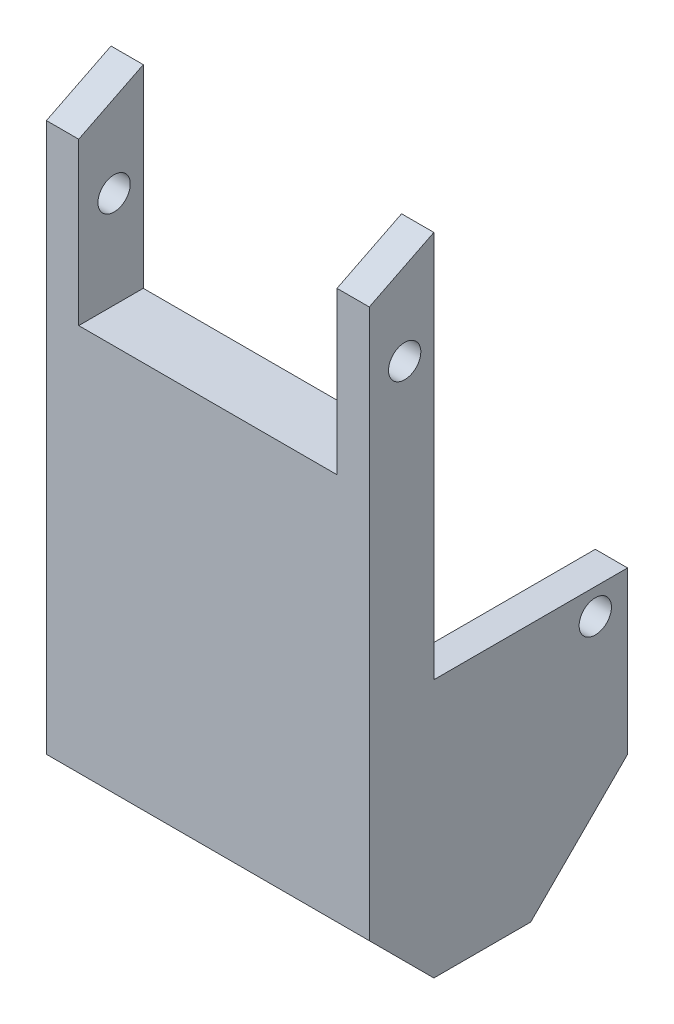
SolidWorks part; units mm, degrees
ref_plane "前视基准面" through (0, 0, 0) normal (0, 0, 1) x (1, 0, 0)
ref_plane "上视基准面" through (0, 0, 0) normal (0, 1, 0) x (1, 0, 0)
ref_plane "右视基准面" through (0, 0, 0) normal (1, 0, 0) x (0, 0, -1)
other "Configuration Table"
sketch "草图1" plane through (0, 0, 0) normal (0, 0, 1) x (1, 0, 0)
  line L1 (2.5, 5) -> (-2.5, 5)
  line L2 (2.5, 5) -> (2.5, -5)
  line L3 (2.5, -5) -> (-2.5, -5)
  line L4 (-2.5, 5) -> (-2.5, -5)
  line L5 (2.5, 5) -> (-2.5, -5) construction
  line L6 (2.5, -5) -> (-2.5, 5) construction
  point P0 (0, 0)
  dimension "D1" = 5
  dimension "D2" = 10
extrude "凸台-拉伸1" add sketch "草图1" along normal blind 4
sketch "草图2" plane through (2.5, 0, 0) normal (1, 0, 0) x (0, 0, -1)
  line L8 (-4, 5) -> (0, 5) construction
  line L9 (-4, -5) -> (-4, 5) construction
  line L10 (-4, 4.5) -> (-3, 5)
  point P0 (-3, 5)
  point P1 (-4, 4.5)
  dimension "D1" = 1
  dimension "D2" = 0.5
extrude "切除-拉伸1" cut sketch "草图2" against normal through all and the other way through all
sketch "草图3" plane through (2.5, 0, 0) normal (1, 0, 0) x (0, 0, -1)
  line L0 (-3, 5) -> (-3, -1)
  line L1 (-3, -1) -> (0, -1)
  line L2 (0, -5) -> (0, 5) construction
  dimension "D1" = 6
extrude "切除-拉伸2" cut sketch "草图3" against normal through all and the other way through all contours L0 L1
sketch "草图6" plane through (0, -1, 0) normal (0, 1, 0) x (1, 0, 0)
  line L0 (2.5, 0) -> (-2.5, 0) construction
  line L1 (-2, -3) -> (2, -3)
  line L2 (-2, -3) -> (-2, 0)
  line L3 (-2, 0) -> (2, 0)
  line L4 (2, -3) -> (2, 0)
  line L5 (-2, -3) -> (2, 0) construction
  line L6 (-2, 0) -> (2, -3) construction
  line L7 (-2.5, 0) -> (-2.5, -3) construction
  point P0 (0, -1.5)
  dimension "D1" = 4
  dimension "D2" = 3
  dimension "D3" = 0.5
extrude "切除-拉伸3" cut sketch "草图6" against normal blind 2.5
sketch "草图7" plane through (0, 0, 3) normal (0, 0, -1) x (-1, 0, 0)
  line L0 (-2.5, 5) -> (2.5, 5) construction
  line L1 (2, 5) -> (-2, 5)
  line L2 (2, 5) -> (2, 2)
  line L3 (2, 2) -> (-2, 2)
  line L4 (-2, 5) -> (-2, 2)
  line L5 (2, 5) -> (-2, 2) construction
  line L6 (2, 2) -> (-2, 5) construction
  line L7 (-2.5, 5) -> (-2.5, -1) construction
  point P0 (0, 3.5)
  dimension "D1" = 4
  dimension "D2" = 3
  dimension "D3" = 0.5
extrude "切除-拉伸4" cut sketch "草图7" against normal blind 2.5
sketch "草图8" plane through (2.5, 0, 0) normal (1, 0, 0) x (0, 0, -1)
  line L0 (-4, -5) -> (-4, 4.5) construction
  line L1 (-4, -5) -> (0, -5) construction
  line L2 (-4, -4) -> (-3, -5)
  point P0 (-4, -4)
  point P1 (-3, -5)
  dimension "D1" = 1
  dimension "D2" = 1
extrude "切除-拉伸5" cut sketch "草图8" against normal through all and the other way through all flip side to cut
sketch "草图9" plane through (2.5, 0, 0) normal (1, 0, 0) x (0, 0, -1)
  line L0 (0, -5) -> (0, -1) construction
  line L1 (-3, -5) -> (0, -5) construction
  line L2 (-1.5, -5) -> (0, -3.5)
  point P0 (0, -3.5)
  point P1 (-1.5, -5)
  dimension "D1" = 2.5
extrude "切除-拉伸10" cut sketch "草图9" against normal blind 5 and the other way through all flip side to cut contours L2
sketch "草图11" plane through (2.5, 0, 0) normal (1, 0, 0) x (0, 0, -1)
  line L0 (-4, -4) -> (-4, 4.5) construction
  line L1 (-3, -5) -> (-1.5, -5) construction
  circle A1 centre (-3.4519, 3.5) radius 0.25
  dimension "D1" = 0.5
  dimension "D2" = 0.5481
  dimension "D3" = 8.5
extrude "切除-拉伸11" cut sketch "草图11" against normal blind 5
sketch "草图12" plane through (2.5, 0, 0) normal (1, 0, 0) x (0, 0, -1)
  line L0 (-3, -1) -> (0, -1) construction
  line L1 (0, -3.5) -> (0, -1) construction
  circle A1 centre (-0.5, -1.4) radius 0.25
  dimension "D1" = 0.5
  dimension "D2" = 0.4
  dimension "D3" = 0.5
extrude "切除-拉伸12" cut sketch "草图12" against normal blind 5
